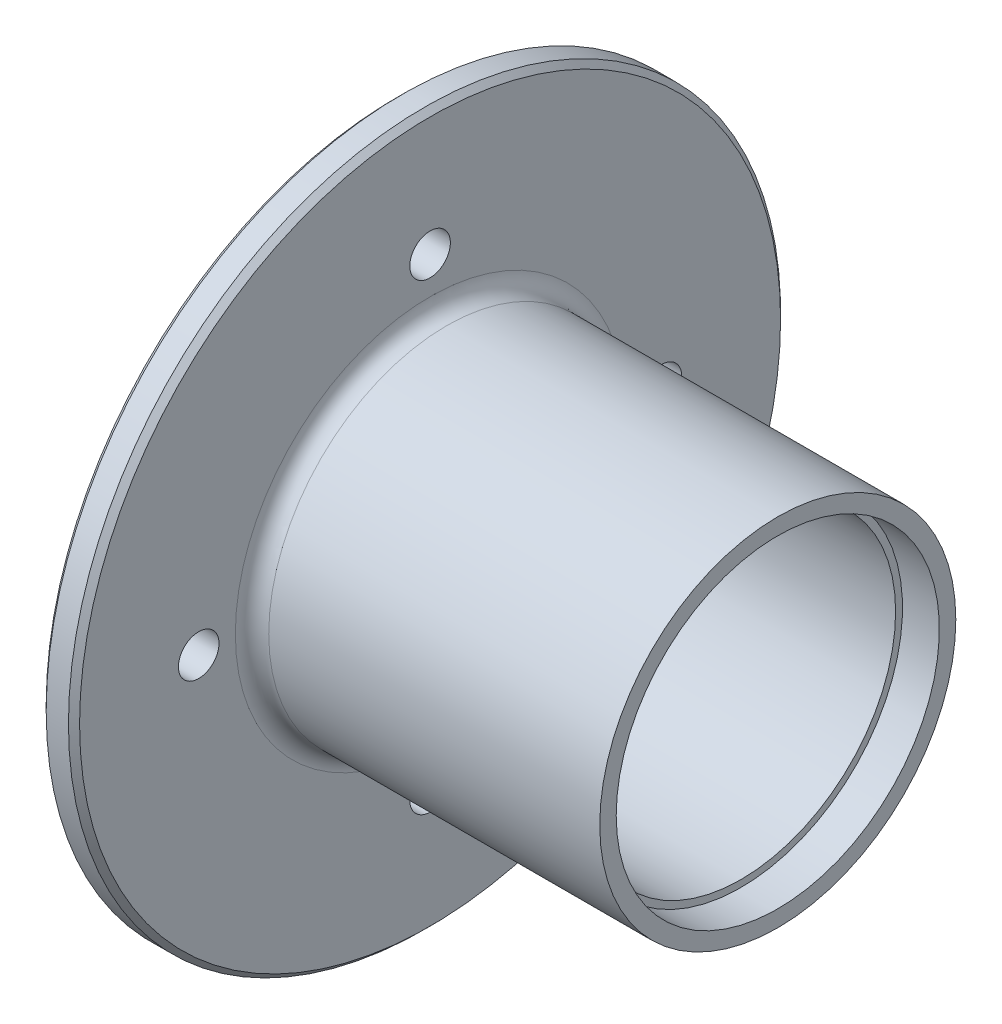
SolidWorks part; units mm, degrees
ref_plane "前视基准面" through (0, 0, 0) normal (0, 0, 1) x (1, 0, 0)
ref_plane "上视基准面" through (0, 0, 0) normal (0, 1, 0) x (1, 0, 0)
ref_plane "右视基准面" through (0, 0, 0) normal (1, 0, 0) x (0, 0, -1)
sketch "Model" plane through (0, 0, 0) normal (0, 0, 1) x (1, 0, 0)
  line L0 (8.1114, 12.5521) -> (8.1114, 17.1503)
  line L1 (8.1114, 17.1503) -> (23.5579, 17.1503)
  line L2 (23.5579, 17.1503) -> (23.5579, 22.0769)
  line L3 (23.5579, 22.0769) -> (52.4792, 22.0769)
  line L4 (52.4792, 22.0769) -> (52.4792, 23.0622)
  line L6 (57.7376, 23.0622) -> (57.7376, 25.4103)
  line L7 (57.7376, 25.4103) -> (10.4936, 25.4103)
  line L8 (8.1114, 27.7925) -> (8.1114, 50.0264)
  line L9 (7.3173, 50.8205) -> (4.141, 50.8205)
  line L10 (3.3469, 50.0264) -> (3.3469, 17.1503)
  line L11 (3.3469, 17.1503) -> (8.1114, 12.5521)
  line L12 (8.1114, 50.0264) -> (7.3173, 50.8205)
  line L13 (4.141, 50.8205) -> (3.3469, 50.0264)
  line L14 (0, 0) -> (65.0877, 0) construction
  line L29 (-167.1623, 0) -> (-110.8944, 0) construction
  line L42 (52.4792, 23.0622) -> (57.7376, 23.0622)
  line L43 (-102.3034, 26.8632) -> (-96.0907, 63.1023)
  line L44 (-96.0907, 63.1023) -> (-91.8357, 63.106)
  line L45 (-126.7312, -63.4202) -> (-139.4363, -63.4202) construction
  line L46 (-139.4363, -63.4202) -> (-139.4363, 61.5599) construction
  line L47 (-139.4363, 61.5599) -> (-126.7312, 61.5599) construction
  line L48 (-104.225, 20.3293) -> (-103.1284, 20.9624) construction
  line L49 (-103.3601, 20.0975) -> (-103.9933, 21.1941) construction
  line L50 (-102.5801, 21.279) -> (-99.281, 23.1837) construction
  line L51 (-104.3099, 21.7425) -> (-106.2146, 25.0415) construction
  line L52 (-104.7733, 20.0127) -> (-108.0724, 18.108) construction
  line L53 (-103.0436, 19.5492) -> (-101.1389, 16.2501) construction
  line L54 (-104.225, -20.3293) -> (-103.1284, -20.9624) construction
  line L55 (-103.9933, -21.1941) -> (-103.3601, -20.0975) construction
  line L56 (-102.5801, -21.279) -> (-99.281, -23.1837) construction
  line L57 (-103.0436, -19.5492) -> (-101.1389, -16.2501) construction
  line L58 (-104.7733, -20.0127) -> (-108.0724, -18.108) construction
  line L59 (-104.3099, -21.7425) -> (-106.2146, -25.0415) construction
  line L60 (-139.4363, -40.6585) -> (-139.4363, -41.9248) construction
  line L61 (-140.0695, -41.2917) -> (-138.8032, -41.2917) construction
  line L62 (-139.4363, -42.5579) -> (-139.4363, -46.3674) construction
  line L63 (-138.1701, -41.2917) -> (-134.3606, -41.2917) construction
  line L64 (-139.4363, -40.0254) -> (-139.4363, -36.216) construction
  line L65 (-140.7026, -41.2917) -> (-144.512, -41.2917) construction
  line L66 (-174.6477, -20.3293) -> (-175.7443, -20.9624) construction
  line L67 (-175.5125, -20.0975) -> (-174.8794, -21.1941) construction
  line L68 (-176.2926, -21.279) -> (-179.5917, -23.1837) construction
  line L69 (-174.5628, -21.7425) -> (-172.6581, -25.0415) construction
  line L70 (-174.0993, -20.0127) -> (-170.8003, -18.108) construction
  line L71 (-175.8291, -19.5492) -> (-177.7338, -16.2501) construction
  line L72 (-174.6477, 20.3293) -> (-175.7443, 20.9624) construction
  line L73 (-174.8794, 21.1941) -> (-175.5125, 20.0975) construction
  line L74 (-176.2926, 21.279) -> (-179.5917, 23.1837) construction
  line L75 (-175.8291, 19.5492) -> (-177.7338, 16.2501) construction
  line L76 (-174.0993, 20.0127) -> (-170.8003, 18.108) construction
  line L77 (-174.5628, 21.7425) -> (-172.6581, 25.0415) construction
  line L78 (-139.4363, 40.6585) -> (-139.4363, 41.9248) construction
  line L79 (-138.8032, 41.2917) -> (-140.0695, 41.2917) construction
  line L80 (-139.4363, 42.5579) -> (-139.4363, 46.3674) construction
  line L81 (-140.7026, 41.2917) -> (-144.512, 41.2917) construction
  line L82 (-139.4363, 40.0254) -> (-139.4363, 36.216) construction
  line L83 (-138.1701, 41.2917) -> (-134.3606, 41.2917) construction
  line L84 (-121.9668, -63.4202) -> (-126.7312, -62.6341) construction
  line L85 (-126.7312, -62.6341) -> (-126.7312, -64.2064) construction
  line L86 (-126.7312, -64.2064) -> (-121.9668, -63.4202) construction
  line L87 (-121.9668, 61.5599) -> (-126.7312, 62.346) construction
  line L88 (-126.7312, 62.346) -> (-126.7312, 60.7738) construction
  line L89 (-126.7312, 60.7738) -> (-121.9668, 61.5599) construction
  line L101 (-101.552, 26.7344) -> (-103.0762, 22.3551)
  line L102 (-103.0762, 22.3551) -> (-103.0547, 26.992)
  line L103 (-103.0547, 26.992) -> (-101.552, 26.7344)
  circle A0 centre (-139.4363, 0) radius 25.4103
  circle A1 centre (-139.4363, 0) radius 50.8205
  arc A2 (8.1114, 27.7925) -> (10.4936, 25.4103) centre (10.4936, 27.7925) ccw
  circle A3 centre (-139.4363, 0) radius 12.5521
  circle A4 centre (-139.4363, 0) radius 17.1503
  circle A5 centre (-139.4363, 0) radius 22.0769
  circle A6 centre (-139.4363, 0) radius 23.0622
  circle A7 centre (-139.4363, 0) radius 24.0475 construction
  circle A9 centre (-139.4363, 0) radius 50.0264
  circle A10 centre (-103.6767, 20.6458) radius 1.8994
  circle A11 centre (-103.6767, -20.6458) radius 1.8994
  circle A12 centre (-139.4363, -41.2917) radius 1.8994
  circle A13 centre (-175.196, -20.6458) radius 1.8994
  circle A14 centre (-175.196, 20.6458) radius 1.8994
  circle A15 centre (-139.4363, 41.2917) radius 1.8994
  text T0 "A" font "ROMANS" height 3.175
  text T1 "A" font "ROMANS" height 3.175
  text T4 "6X, Ø .149\r\nØ 3.25 BC" font "TXT" height 4.572
  point P11 (-207.5827, -142.5336)
  point P12 (-207.5827, -142.5336)
  point P13 (-207.5827, -142.5336)
  dimension "D2" = 89.5644
  dimension "D3" = 91.8357
  dimension "D4" = 96.0907
  dimension "D5" = 101.552
  dimension "D6" = 102.3034
  dimension "D7" = 103.0762
  dimension "D8" = 119.6473
  dimension "D9" = 120.264
  dimension "D10" = 22.3551
  dimension "D11" = 26.7344
  dimension "D1" = 47.244
  dimension "D12" = 56.2778
  dimension "D13" = 61.119
  dimension "D14" = 63.106
  dimension "D15" = 68.7024
revolve "旋转1" add sketch "Model" angle 360 about L14
hole_wizard "#12 间隙孔1" positions "草图2" profile "草图3" hole size "#12" standard "ANSI Inch" end condition through all
sketch "草图2" plane through (3.3469, 0, 0) normal (-1, 0, 0) x (0, 0, 1)
  point P0 (0, 33.02)
  dimension "D1" = 33.02
sketch "草图3" plane through (3.3469, 33.02, 0) normal (0, 1, 0) x (0, 0, 1)
  line L0 (0, 0) -> (0, 54.3906)
  line L1 (0, 54.3906) -> (2.8956, 54.3906)
  line L2 (2.8956, 54.3906) -> (2.8956, 0)
  line L5 (2.8956, 0) -> (0, 0)
  line L11 (0, -6.35) -> (0, 107.95) construction
  dimension "通孔孔直径" = 5.7912
  dimension "通孔孔深度" = 54.3906
ref_axis "基准轴1" through (57.7376, 0, 0) along (-1, 0, 0)
pattern_circular "阵列(圆周)1" count 4 over 360 about axis through (57.7376, 0, 0) along (-1, 0, 0) of "#12 间隙孔1"
